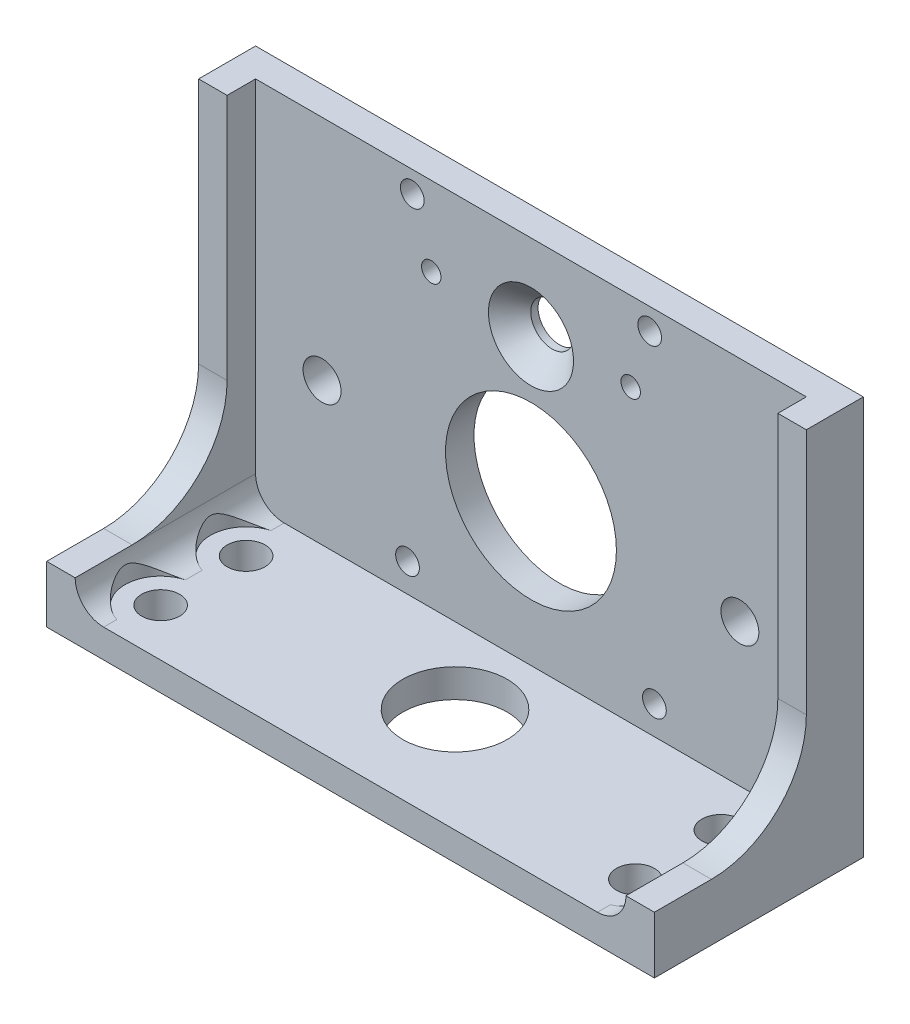
SolidWorks part; units mm, degrees
material "6063-O"
ref_plane "Front" through (0, 0, 0) normal (0, 0, 1) x (1, 0, 0)
ref_plane "Top" through (0, 0, 0) normal (0, 1, 0) x (1, 0, 0)
ref_plane "Right" through (0, 0, 0) normal (1, 0, 0) x (0, 0, -1)
sketch "Sketch1" plane through (0, 0, 0) normal (0, 0, 1) x (1, 0, 0)
  line L1 (-32, -15) -> (32, -15)
  line L2 (-32, -15) -> (-32, 24)
  line L3 (-32, 24) -> (32, 24)
  line L4 (32, -15) -> (32, 24)
  circle A0 centre (0, 0) radius 22 construction
  circle A4 centre (0, 0) radius 9
  point P3 (-22, 0)
  point P4 (22, 0)
  point P5 (0, 22)
  dimension "D1" = 44
  dimension "D2" = 18
  dimension "D3" = 24
  dimension "D6" = 15
extrude "Boss-Extrude1" add sketch "Sketch1" along normal blind 3
sketch "Sketch2" plane through (0, 0, 3) normal (0, 0, 1) x (1, 0, 0)
  line L0 (-32, -15) -> (32, -15) construction
  line L1 (-32, 24) -> (-29, 24)
  line L2 (-32, 24) -> (-32, -15)
  line L3 (-32, -15) -> (-29, -15)
  line L4 (-29, 24) -> (-29, -15)
  line L6 (32, 24) -> (29, 24)
  line L7 (32, 24) -> (32, -15)
  line L8 (32, -15) -> (29, -15)
  line L9 (29, 24) -> (29, -15)
  dimension "D1" = 3
  dimension "D2" = 3
extrude "Boss-Extrude2" add sketch "Sketch2" along normal blind 3
sketch "Sketch3" plane through (0, -15, 0) normal (0, -1, 0) x (1, 0, 0)
  line L0 (32, 6) -> (32, 0) construction
  line L1 (-32, 0) -> (32, 0)
  line L2 (-32, 0) -> (-32, 22)
  line L3 (-32, 22) -> (32, 22)
  line L4 (32, 0) -> (32, 22)
  dimension "D1" = 22
extrude "Boss-Extrude3" add sketch "Sketch3" along normal blind 3
sketch "Sketch4" plane through (0, -15, 0) normal (0, 1, 0) x (1, 0, 0)
  line L0 (32, -22) -> (-32, -22) construction
  line L1 (-32, -6) -> (-29, -6)
  line L2 (-32, -6) -> (-32, -22)
  line L3 (-32, -22) -> (-29, -22)
  line L4 (-29, -6) -> (-29, -22)
  line L5 (-29, -6) -> (-29, -3) construction
  line L6 (0, 0) -> (0, -16.0026) construction
  line L7 (29, -6) -> (29, -22)
  line L8 (32, -22) -> (29, -22)
  line L9 (32, -6) -> (32, -22)
  line L10 (32, -6) -> (29, -6)
extrude "Boss-Extrude4" add sketch "Sketch4" along normal blind 3
fillet "Fillet1" radius 10 2 edges at (-30.5, -12, 6) (30.5, -12, 6)
sketch "Sketch5" plane through (0, 0, 0) normal (0, 0, -1) x (-1, 0, 0)
  point P0 (0, 15)
  point P1 (22, 0)
  point P3 (-22, 0)
sketch "Sketch6" plane through (0, 0, 3) normal (0, 0, 1) x (1, 0, 0)
  point P0 (-10.5, 15.66)
  point P1 (10.5, 15.66)
  point P3 (0, 15)
hole_wizard "Ø4.0 (4) Diameter Hole1" positions "Sketch8" profile "Sketch7" hole size "Ø4.0" standard "ISO"
sketch "Sketch8" plane through (0, 0, 0) normal (0, 0, -1) x (-1, 0, 0)
  point P0 (-22, 0)
  point P3 (22, 0)
sketch "Sketch7" plane through (22, 0, 0) normal (1, 0, 0) x (0, 1, 0)
  line L0 (0, 0) -> (0, 16.2017)
  line L1 (0, 16.2017) -> (2, 15)
  line L2 (2, 15) -> (2, 0)
  line L5 (2, 0) -> (0, 0)
  line L10 (0, 16.2017) -> (-2, 15) construction
  line L11 (0, -6.35) -> (0, 107.95) construction
  dimension "Hole Dia." = 4
  dimension "Hole Depth" = 15
  dimension "Drill Angle" = 118
hole_wizard "CSK for M4 Hex Socket Countersunk Cap Screw1" positions "Sketch13" profile "Sketch12" countersink size "M4" standard "ISO"
sketch "Sketch13" plane through (0, 0, 3) normal (0, 0, 1) x (1, 0, 0)
  point P0 (0, 15)
sketch "Sketch12" plane through (0, 15, 3) normal (1, 0, 0) x (0, -1, 0)
  line L0 (0, 0) -> (0, 11.3519)
  line L1 (0, 11.3519) -> (2.25, 10)
  line L2 (2.25, 10) -> (2.25, 2.23)
  line L3 (2.25, 2.23) -> (4.48, 0)
  line L5 (4.48, 0) -> (0, 0)
  line L6 (-2.25, 2.23) -> (-4.48, 0) construction
  line L10 (0, 11.3519) -> (-2.25, 10) construction
  line L11 (0, -6.35) -> (0, 107.95) construction
  dimension "Hole Dia." = 4.5
  dimension "Hole Depth" = 10
  dimension "Near C'Sink Dia." = 8.96
  dimension "Near C'Sink Angle" = 90
  dimension "Drill Angle" = 118
hole_wizard "M2.5 Tapped Hole1" positions "Sketch15" profile "Sketch14" tap size "M2.5" standard "ISO"
sketch "Sketch15" plane through (0, 0, 3) normal (0, 0, 1) x (1, 0, 0)
  point P0 (-10.5, 15.66)
  point P3 (10.5, 15.66)
sketch "Sketch14" plane through (-10.5, 15.66, 3) normal (1, 0, 0) x (0, -1, 0)
  line L0 (0, 0) -> (0, 7.8659)
  line L1 (0, 7.8659) -> (1.025, 7.25)
  line L2 (1.025, 7.25) -> (1.025, 0)
  line L5 (1.025, 0) -> (0, 0)
  line L10 (0, 7.8659) -> (-1.025, 7.25) construction
  line L11 (0, -6.35) -> (0, 107.95) construction
  dimension "Tap Drill Dia." = 2.05
  dimension "Tap Drill Depth" = 7.25
  dimension "Drill Angle" = 118
cosmetic thread "Hole Thread1" parameters "D1"=3, "D2"=2.5
cosmetic thread "Hole Thread2" parameters "D1"=3, "D2"=2.5
sketch "Sketch16" plane through (0, 0, 3) normal (0, 0, 1) x (1, 0, 0)
  point P0 (-12.5, 21.75)
  point P1 (12.5, 21.75)
  point P3 (13, -12)
  point P5 (-13, -12)
hole_wizard "M3 Tapped Hole1" positions "Sketch18" profile "Sketch17" tap size "M3" standard "ISO"
sketch "Sketch18" plane through (0, 0, 3) normal (0, 0, 1) x (1, 0, 0)
  point P0 (-12.5, 21.75)
  point P3 (12.5, 21.75)
  point P6 (13, -12)
  point P9 (-13, -12)
sketch "Sketch17" plane through (-12.5, 21.75, 3) normal (1, 0, 0) x (0, -1, 0)
  line L0 (0, 0) -> (0, 9.2511)
  line L1 (0, 9.2511) -> (1.25, 8.5)
  line L2 (1.25, 8.5) -> (1.25, 0)
  line L5 (1.25, 0) -> (0, 0)
  line L10 (0, 9.2511) -> (-1.25, 8.5) construction
  line L11 (0, -6.35) -> (0, 107.95) construction
  dimension "Tap Drill Dia." = 2.5
  dimension "Tap Drill Depth" = 8.5
  dimension "Drill Angle" = 118
cosmetic thread "Hole Thread3" parameters "D1"=3, "D2"=3
cosmetic thread "Hole Thread4" parameters "D1"=3, "D2"=3
cosmetic thread "Hole Thread5" parameters "D1"=3, "D2"=3
cosmetic thread "Hole Thread6" parameters "D1"=3, "D2"=3
fillet "Fillet4" radius 3 2 edges at (29, -15, 12.5)
sketch "Sketch19" plane through (0, -18, 0) normal (0, -1, 0) x (1, 0, 0)
  line L0 (-32, 22) -> (-32, 0) construction
  line L3 (-32, 0) -> (32, 0) construction
  circle A0 centre (-25, 8) radius 2
  circle A1 centre (25, 8) radius 2
  circle A2 centre (-25, 17) radius 2
  circle A3 centre (25, 17) radius 2
  dimension "D1" = 7
  dimension "D4" = 9
  dimension "D5" = 9
  dimension "D2" = 8
  dimension "D3" = 8
extrude "Cut-Extrude1" cut sketch "Sketch19" against normal blind 10
sketch "Sketch20" plane through (0, -15, 0) normal (0, 1, 0) x (1, 0, 0)
  line L0 (32, 0) -> (-32, 0) construction
  circle A0 centre (0, -11) radius 5.5
  dimension "D1" = 11
  dimension "D2" = 11
extrude "Cut-Extrude2" cut sketch "Sketch20" against normal blind 10
sketch "Sketch21" plane through (0, -15, 0) normal (0, 1, 0) x (1, 0, 0)
  circle A0 centre (-25, -8) radius 3.75
  circle A1 centre (-25, -17) radius 3.75
  circle A2 centre (25, -8) radius 3.75
  circle A3 centre (25, -17) radius 3.75
  dimension "D1" = 7.5
  dimension "D2" = 7.5
  dimension "D3" = 7.5
  dimension "D4" = 7.5
extrude "Cut-Extrude3" cut sketch "Sketch21" along normal blind 10
